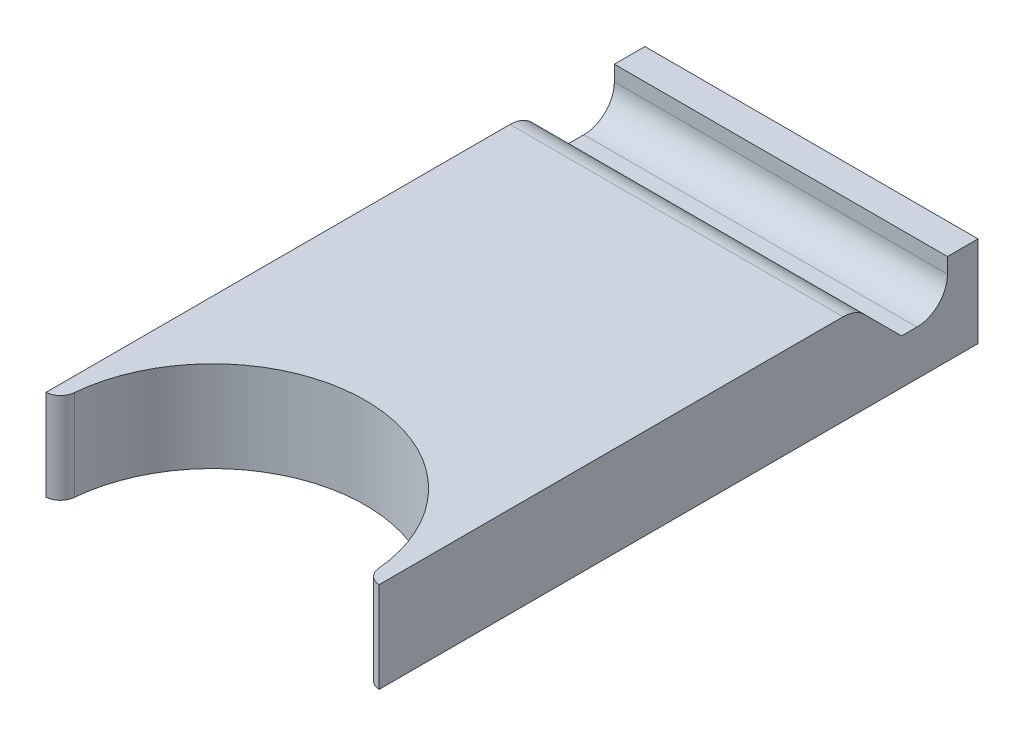
SolidWorks part; units mm, degrees
ref_plane "Front Plane" through (0, 0, 0) normal (0, 0, 1) x (1, 0, 0)
ref_plane "Top Plane" through (0, 0, 0) normal (0, 1, 0) x (1, 0, 0)
ref_plane "Right Plane" through (0, 0, 0) normal (1, 0, 0) x (0, 0, -1)
sketch "Sketch1" plane through (0, 0, 0) normal (0, 1, 0) x (1, 0, 0)
  line L0 (5, 0) -> (5.45, 0)
  line L1 (-5.45, 0) -> (-5, 0)
  line L2 (-5.45, 0) -> (-5.45, 19.6)
  line L3 (-5.45, 19.6) -> (5.45, 19.6)
  line L4 (5.45, 0) -> (5.45, 19.6)
  arc A0 (5, 0) -> (-5, 0) centre (0, 0) ccw
  dimension "D1" = 10
  dimension "D2" = 5.45
  dimension "D3" = 10.9
  dimension "D4" = 19.6
extrude "Boss-Extrude1" add sketch "Sketch1" along normal blind 2.97
fillet "Fillet1" radius 0.5 2 edges at (5, 1.485, 0) (-5, 1.485, 0)
sketch "Sketch2" plane through (0, 2.97, 0) normal (0, 1, 0) x (1, 0, 0)
  line L0 (-5.45, 19.6) -> (-5.45, 0) construction
  line L1 (-5.45, 18.6) -> (5.45, 18.6)
  line L2 (-5.45, 18.6) -> (-5.45, 17.6)
  line L3 (-5.45, 17.6) -> (5.45, 17.6)
  line L4 (5.45, 18.6) -> (5.45, 17.6)
  line L5 (5.45, 0) -> (5.45, 19.6) construction
  line L6 (5.45, 19.6) -> (-5.45, 19.6) construction
  dimension "D1" = 1
  dimension "D2" = 1
extrude "Cut-Extrude1" cut sketch "Sketch2" against normal blind 1.5
chamfer "Chamfer1" distance 2 angle 45 1 edges at (0, 2.97, -17.6)
fillet "Fillet2" radius 1 2 edges at (0, 1.47, -18.6) (0, 2.97, -15.6)
